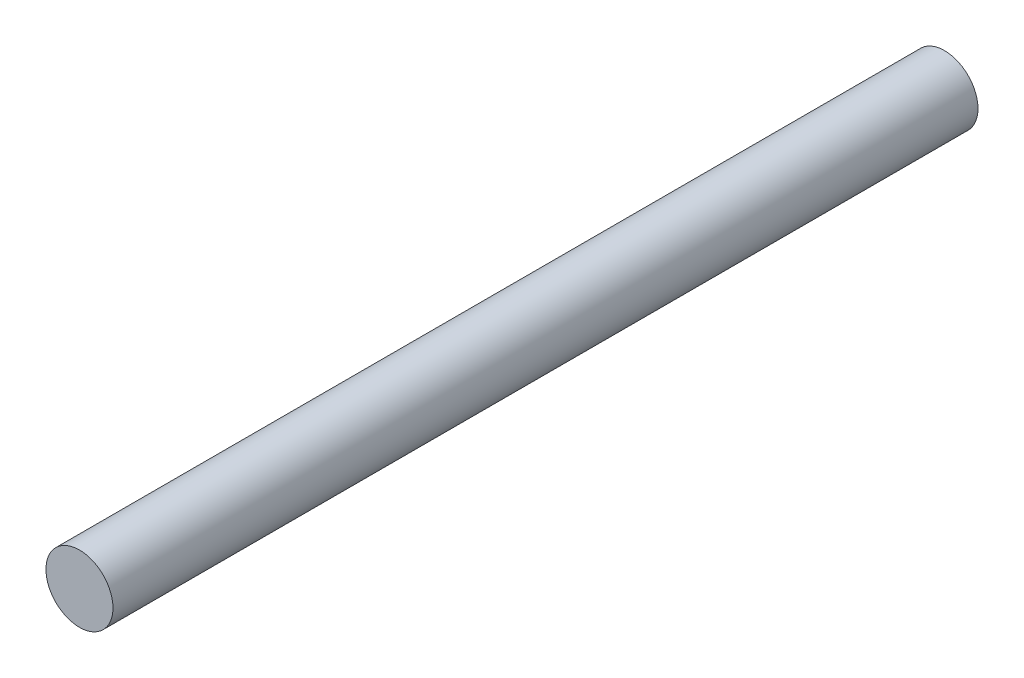
SolidWorks part; units mm, degrees
ref_plane "Front Plane" through (0, 0, 0) normal (0, 0, 1) x (1, 0, 0)
ref_plane "Top Plane" through (0, 0, 0) normal (0, 1, 0) x (1, 0, 0)
ref_plane "Right Plane" through (0, 0, 0) normal (1, 0, 0) x (0, 0, -1)
sketch "Sketch2" plane through (0, 0, 0) normal (0, 0, 1) x (1, 0, 0)
  circle A0 centre (0, 0) radius 3.875
  dimension "D1" = 7.75
extrude "Boss-Extrude1" add sketch "Sketch2" along normal blind 100
